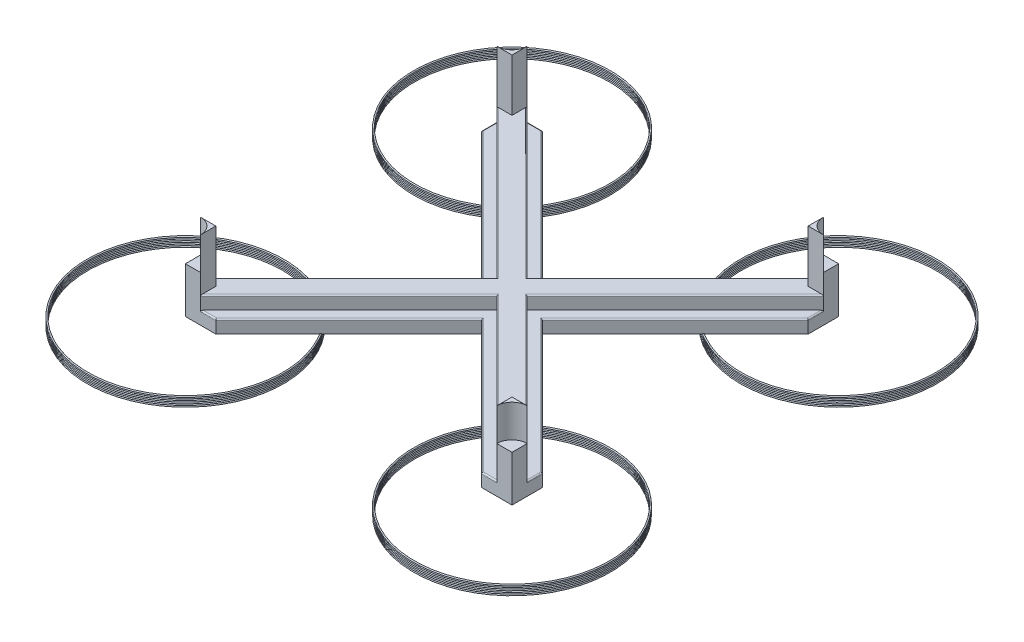
SolidWorks part; units mm, degrees
material "ABS"
ref_plane "Front Plane" through (0, 0, 0) normal (0, 0, 1) x (1, 0, 0)
ref_plane "Top Plane" through (0, 0, 0) normal (0, 1, 0) x (1, 0, 0)
ref_plane "Right Plane" through (0, 0, 0) normal (1, 0, 0) x (0, 0, -1)
sketch "Sketch1" plane through (0, 0, 0) normal (0, 1, 0) x (1, 0, 0)
  line L0 (-11.8367, 0) -> (-63.5, 51.6633)
  line L1 (-63.5, -63.5) -> (-51.6633, -63.5)
  line L2 (-63.5, -63.5) -> (-63.5, -51.6633)
  line L3 (-63.5, 63.5) -> (-51.6633, 63.5)
  line L4 (63.5, -63.5) -> (63.5, -51.6633)
  line L5 (-63.5, -63.5) -> (63.5, 63.5) construction
  line L6 (-63.5, 63.5) -> (63.5, -63.5) construction
  line L7 (0, -11.8367) -> (51.6633, -63.5)
  line L8 (0, 11.8367) -> (-51.6633, 63.5)
  line L9 (11.8367, 0) -> (63.5, -51.6633)
  line L12 (-63.5, -51.6633) -> (-11.8367, 0)
  line L13 (63.5, 51.6633) -> (11.8367, 0)
  line L16 (51.6633, 63.5) -> (63.5, 63.5)
  line L17 (63.5, 51.6633) -> (63.5, 63.5)
  line L18 (-63.5, 51.6633) -> (-63.5, 63.5)
  line L19 (51.6633, -63.5) -> (63.5, -63.5)
  line L20 (0, 11.8367) -> (51.6633, 63.5)
  line L21 (0, -11.8367) -> (-51.6633, -63.5)
  point P0 (0, 0)
extrude "Boss-Extrude1" add sketch "Sketch1" along normal blind 5.08
ref_plane "Plane3" through (0, 0, 0) normal (0, 0, -1) x (-1, 0, 0)
ref_plane "Plane1" through (0, 0, 0) normal (0.7071, 0, -0.7071) x (-0.7071, 0, -0.7071)
ref_plane "Plane2" through (0, 0, 0) normal (1, 0, 0) x (0, 0, -1)
sketch "Sketch3" plane through (0, 5.08, 0) normal (0, 1, 0) x (1, 0, 0)
  line L0 (-63.5, -63.5) -> (63.5, 63.5) construction
  line L1 (-63.5, -63.5) -> (-57.5816, -63.5)
  line L2 (-63.5, -63.5) -> (-63.5, -57.5816)
  line L3 (-63.5, -57.5816) -> (-57.5816, -57.5816)
  line L4 (-57.5816, -63.5) -> (-57.5816, -57.5816)
  line L5 (-63.5, -63.5) -> (-63.5, -51.6633) construction
  line L8 (1.9757, -1.9757) -> (-1.9757, 1.9757) construction
  line L9 (57.5816, 63.5) -> (57.5816, 57.5816)
  line L10 (63.5, 57.5816) -> (57.5816, 57.5816)
  line L11 (63.5, 63.5) -> (63.5, 57.5816)
  line L12 (63.5, 63.5) -> (57.5816, 63.5)
  line L13 (2.794, 0) -> (-2.794, 0) construction
  line L14 (-63.5, 57.5816) -> (-57.5816, 57.5816)
  line L15 (-57.5816, 63.5) -> (-57.5816, 57.5816)
  line L16 (-63.5, 63.5) -> (-57.5816, 63.5)
  line L17 (-63.5, 63.5) -> (-63.5, 57.5816)
  line L18 (0, -2.794) -> (0, 2.794) construction
  line L19 (63.5, -57.5816) -> (57.5816, -57.5816)
  line L20 (57.5816, -63.5) -> (57.5816, -57.5816)
  line L21 (63.5, -63.5) -> (57.5816, -63.5)
  line L22 (63.5, -63.5) -> (63.5, -57.5816)
extrude "Boss-Extrude2" add sketch "Sketch3" along normal blind 38.1
sketch "Sketch4" plane through (0, 0, 0) normal (0, -1, 0) x (1, 0, 0)
  circle A4 centre (-63.5, 63.5) radius 38.1
  point P12 (0, 0)
  point P14 (0, 0)
  point P21 (0, 0)
ref_plane "Plane4" through (0, 0, 0) normal (0.7071, 0, 0.7071) x (0.7071, 0, -0.7071)
sweep "Sweep11" add path "Sketch4" circular profile diameter 0.508 parameters "D3"=0.508
ref_axis "Axis1" through (0, 0, 0) along (0, 1, 0)
pattern_circular "CirPattern1" count 4 over 360 about axis through (0, 0, 0) along (0, 1, 0) of "Sweep11"
sketch "Sketch5" plane through (0, 43.18, 0) normal (0, 1, 0) x (1, 0, 0)
  circle A0 centre (63.5, -63.5) radius 5.9184
extrude "Cut-Extrude1" cut sketch "Sketch5" against normal blind 25.4
pattern_circular "CirPattern2" count 4 over 360 about axis through (0, 0, 0) along (0, 1, 0) of "Cut-Extrude1" reverse direction yes
ref_plane "Plane5" through (0, -0.508, 0) normal (0, -1, 0) x (-1, 0, 0)
ref_axis "Axis2" through (-63.5, 17.78, 63.5) along (0, -1, 0)
sketch "Sketch14" plane through (0, -0.508, 0) normal (0, -1, 0) x (-1, 0, 0)
  circle A0 centre (63.5, -63.5) radius 38.1
sweep "Sweep13" add path "Sketch14" circular profile diameter 0.508 parameters "D3"=0.508
pattern_circular "CirPattern8" count 4 over 360 about axis through (0, 0, 0) along (0, 1, 0) of bodies 109
pattern_linear "LPattern16" count 6 spacing 0.5588 along (0, -1, 0) of bodies 121 120 122 109
sketch "Sketch84" plane through (0, 5.08, 0) normal (0, 1, 0) x (1, 0, 0)
  line L0 (-63.5, 57.5816) -> (-5.9184, 0)
  line L1 (57.5816, 63.5) -> (0, 5.9184)
  line L2 (-57.5816, 63.5) -> (0, 5.9184)
  line L3 (63.5, 57.5816) -> (5.9184, 0)
  line L4 (5.9184, 0) -> (63.5, -57.5816)
  line L5 (-5.9184, 0) -> (-63.5, -57.5816)
  line L6 (0, -5.9184) -> (57.5816, -63.5)
  line L7 (0, -5.9184) -> (-57.5816, -63.5)
  line M1 (57.5816, -57.5816) -> (63.5, -57.5816)
  line M6 (63.5, 57.5816) -> (57.5816, 57.5816)
  line M7 (57.5816, 57.5816) -> (57.5816, 63.5)
  line M12 (-57.5816, 63.5) -> (-57.5816, 57.5816)
  line M13 (-57.5816, 57.5816) -> (-63.5, 57.5816)
  line M18 (-63.5, -57.5816) -> (-57.5816, -57.5816)
  line M19 (-57.5816, -57.5816) -> (-57.5816, -63.5)
  line M24 (57.5816, -63.5) -> (57.5816, -57.5816)
extrude "Boss-Extrude3" add sketch "Sketch84" along normal blind 5.08 contours L7 L6 L4 L3 L1 L2 L0 L5 M24 M1 M6 M7 M12 M13 M18 M19 region at (0, 5.08, 0)
fillet "Fillet1" radius 0.508 24 edges at (-54.6224, 5.08, -63.5) (-63.5, 5.08, -54.6224) (54.6224, 5.08, -63.5) (63.5, 5.08, -54.6224) (54.6224, 5.08, 63.5) (63.5, 5.08, 54.6224) (-63.5, 5.08, 54.6224) (-54.6224, 5.08, 63.5) (25.8316, 5.08, -37.6684) (-25.8316, 5.08, -37.6684) (-37.6684, 5.08, 25.8316) (-37.6684, 5.08, -25.8316) (37.6684, 5.08, 25.8316) (37.6684, 5.08, -25.8316) (25.8316, 5.08, 37.6684) (-25.8316, 5.08, 37.6684) (34.7092, 10.16, 28.7908) (34.7092, 10.16, -28.7908) (28.7908, 10.16, -34.7092) (-28.7908, 10.16, -34.7092) (-34.7092, 10.16, -28.7908) (-34.7092, 10.16, 28.7908) (28.7908, 10.16, 34.7092) (-28.7908, 10.16, 34.7092)
sketch "Sketch85" plane through (0, 43.18, 0) normal (0, 1, 0) x (1, 0, 0)
  line L1 (-63.5, -63.5) -> (70.1925, -63.5)
  line L2 (-63.5, -63.5) -> (-63.5, 70.1925)
  line L3 (-63.5, 70.1925) -> (70.1925, 70.1925)
  line L4 (70.1925, -63.5) -> (70.1925, 70.1925)
extrude "Cut-Extrude2" cut sketch "Sketch85" against normal blind 12.7
